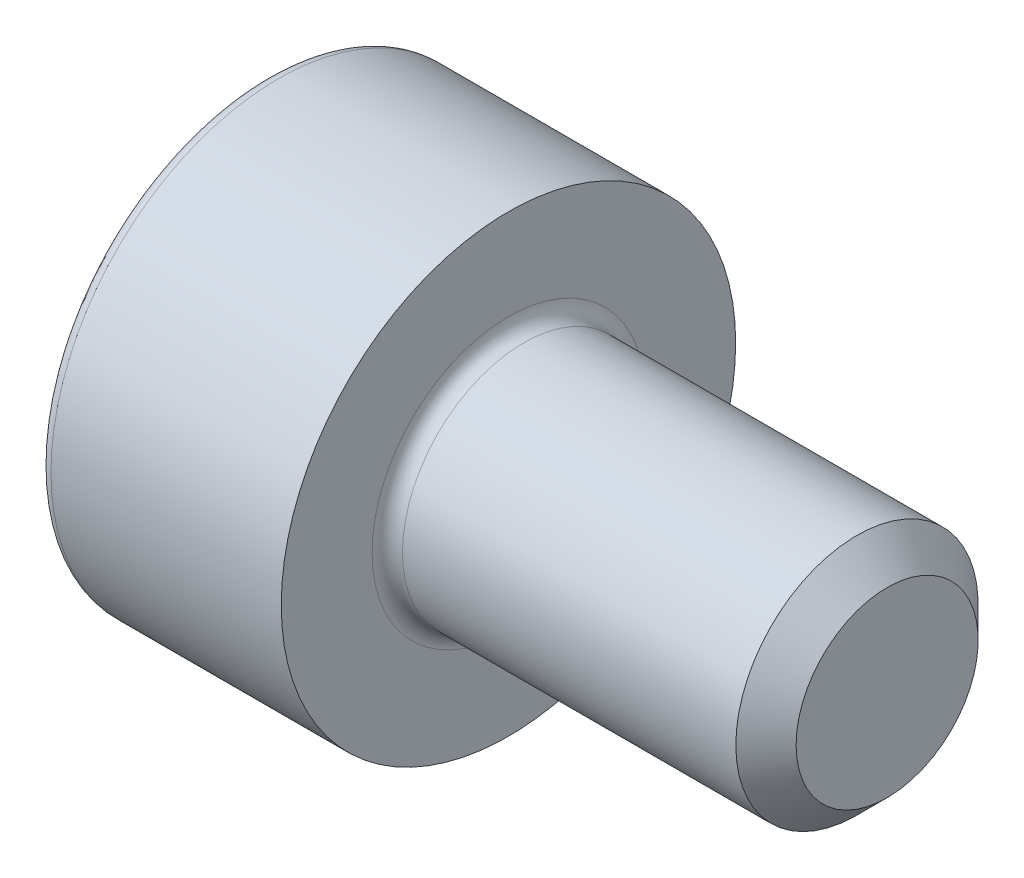
SolidWorks part; units mm, degrees
ref_plane "Front Plane" through (0, 0, 0) normal (0, 0, 1) x (1, 0, 0)
ref_plane "Top Plane" through (0, 0, 0) normal (0, 1, 0) x (1, 0, 0)
ref_plane "Right Plane" through (0, 0, 0) normal (1, 0, 0) x (0, 0, -1)
sketch "BodySke" plane through (0, 0, 0) normal (0, 0, 1) x (1, 0, 0)
  line L0 (0, 0) -> (5.8492, 0) construction
  line L1 (0, 0) -> (0, 1.5)
  line L2 (0, 1.5) -> (1.6, 1.5)
  line L3 (1.6, 1.5) -> (1.6, 0.8)
  line L4 (1.6, 0.8) -> (3.901, 0.8)
  line L5 (3.901, 0.8) -> (4.1, 0.601)
  line L6 (4.1, 0.601) -> (4.1, 0)
  line L7 (4.1, 0) -> (0, 0)
  line L8 (1.6, 0) -> (1.6, 0.601) construction
  line L9 (1.95, 1.5877) -> (1.95, 0.9267) construction
  dimension "Thread_length" = 2.5
  dimension "Thread_minor" = 1.202
  dimension "Advance" = 0.35
revolve "BaseBody" add sketch "BodySke" angle 360 about L0
cosmetic thread "ThreadCosmetic" [suppressed] parameters "Thread_length"=2.5, "Thread_minor"=1.202
fillet "Fillet1" radius 0.1 1 edges at (1.6, 0, 0.8)
fillet "Fillet2" radius 0.08 1 edges at (0, 0, 1.5)
sketch "HexSke" plane through (0, 0, 0) normal (1, 0, 0) x (0, 0, -1)
  line L1 (0, 0.866) -> (-0.75, 0.433)
  line L2 (-0.75, 0.433) -> (-0.75, -0.433)
  line L3 (-0.75, -0.433) -> (0, -0.866)
  line L4 (0, -0.866) -> (0.75, -0.433)
  line L5 (0.75, -0.433) -> (0.75, 0.433)
  line L6 (0.75, 0.433) -> (0, 0.866)
  circle A0 centre (0, 0) radius 0.75 construction
extrude "Hex" cut sketch "HexSke" along normal blind 0.7
sketch "Hex-PreBroachSke" plane through (0, 0, 0) normal (0, 0, 1) x (1, 0, 0)
  line L0 (0, 0) -> (4.7325, 0) construction
  line L1 (0, 1.42) -> (0, -1.42) construction
  line L2 (0, 0) -> (0, 0.75)
  line L3 (0, 0.75) -> (0.7, 0.75)
  line L4 (0.7, 0.75) -> (1.133, 0)
  line L5 (1.133, 0) -> (0, 0)
  dimension "D1" = 1.5
revolve "Hex-PreBroach" cut sketch "Hex-PreBroachSke" angle 360 about L0
sketch "ThdSchSke" plane through (0, 0, 0) normal (0, 0, 1) x (1, 0, 0)
  line L0 (0, 0) -> (4.4125, 0) construction
  line L1 (0, 1.42) -> (0, -1.42) construction
  line L2 (3.551, 1.0298) -> (3.551, 0.8)
  line L3 (3.551, 1.0298) -> (3.7808, 1.0298)
  line L4 (3.7808, 1.0298) -> (3.7808, 0.8)
  line L5 (3.7808, 0.8) -> (3.6659, 0.601)
  line L6 (3.6659, 0.601) -> (3.551, 0.8)
  dimension "D1" = 0.35
revolve "ThreadSchematic" [suppressed] cut sketch "ThdSchSke" angle 360 about L0
pattern_linear "ThdSchPat" [suppressed] of bodies 116
equation "\"Thread_length@ThreadCosmetic\" = \"Thread_length@BodySke\""
equation "\"Thread_minor@ThreadCosmetic\" = \"Thread_minor@BodySke\""
equation "\"Hex_depth@Hex-PreBroachSke\" = \"Hex_length@Hex\""
equation "\"D1@Hex-PreBroachSke\" = \"Hex_size@HexSke\""
equation "\"D1@ThdSchSke\" = \"Advance@BodySke\""
equation "\"Advance@ThdSchPat\" = \"Advance@BodySke\""
equation "\"Tooth_Num@ThdSchPat\" =  int( \"Thread_length@BodySke\" / \"Advance@BodySke\" )  - 1"
